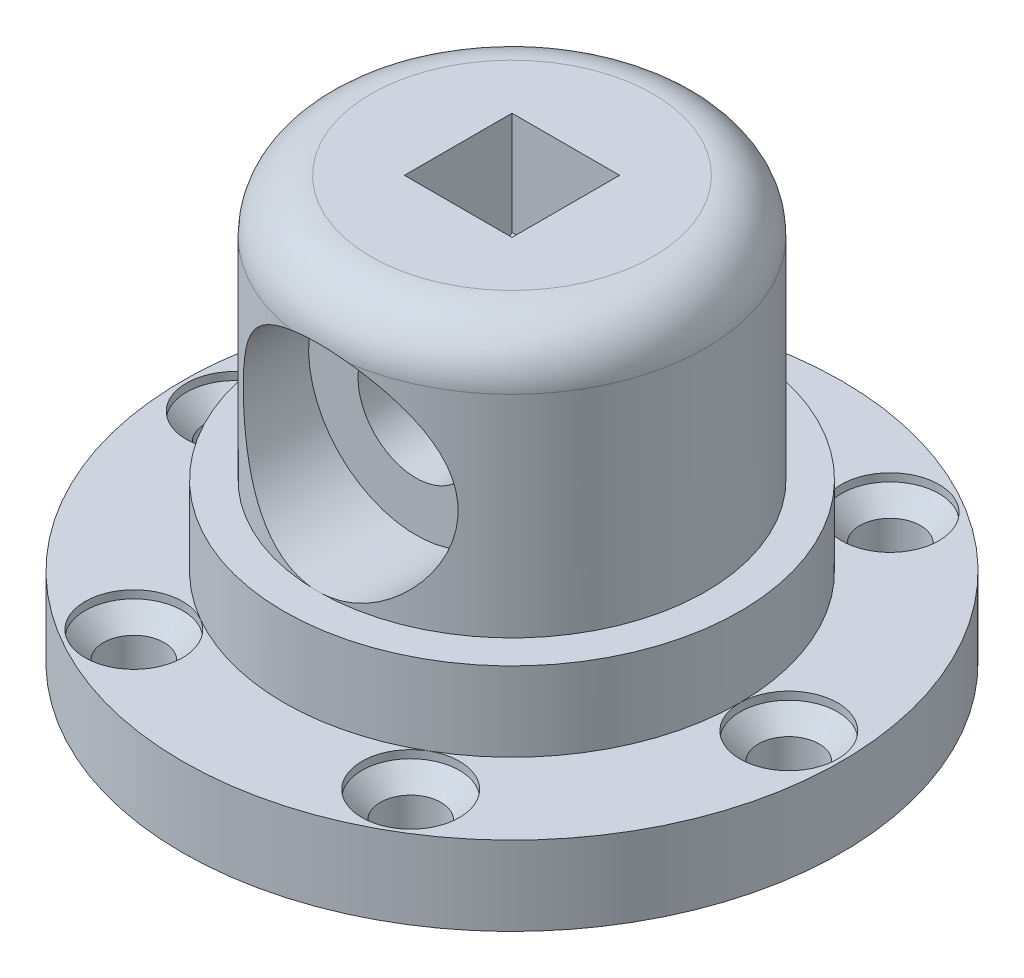
SolidWorks part; units mm, degrees
material "尼龙 101"
ref_plane "前视基准面" through (0, 0, 0) normal (0, 0, 1) x (1, 0, 0)
ref_plane "上视基准面" through (0, 0, 0) normal (0, 1, 0) x (1, 0, 0)
ref_plane "右视基准面" through (0, 0, 0) normal (1, 0, 0) x (0, 0, -1)
sketch "草图1" plane through (0, 0, 0) normal (0, 1, 0) x (1, 0, 0)
  circle A0 centre (0, 0) radius 12.5
  dimension "D1" = 25
extrude "凸台-拉伸1" add sketch "草图1" along normal blind 6
sketch "草图2" plane through (0, 6, 0) normal (0, 1, 0) x (1, 0, 0)
  line L0 (4.1, 4.1) -> (-4.1, 4.1) construction
  line L1 (2.5, 2.5) -> (-2.5, 2.5) construction
  line L2 (2.5, 2.5) -> (2.5, -2.5) construction
  line L3 (2.5, -2.5) -> (-2.5, -2.5) construction
  line L4 (-2.5, 2.5) -> (-2.5, -2.5) construction
  line L5 (2.5, 2.5) -> (-2.5, -2.5) construction
  line L6 (2.5, -2.5) -> (-2.5, 2.5) construction
  line L7 (-4.1, 4.1) -> (-4.1, -4.1) construction
  line L8 (4.1, -4.1) -> (-4.1, -4.1) construction
  line L9 (4.1, 4.1) -> (4.1, -4.1) construction
  line L11 (4.1, 4.1) -> (-4.1, 4.1) construction
  line L12 (4.1, 4.1) -> (4.1, 6.1) construction
  line L13 (4.1, 6.1) -> (-4.1, 6.1) construction
  line L14 (-4.1, 4.1) -> (-4.1, 6.1) construction
  circle A0 centre (0, 0) radius 5.7983 construction
  circle A1 centre (0, 0) radius 7.3498
  point P0 (0, 0)
  dimension "D1" = 5
  dimension "D2" = 5
  dimension "D4" = 2
  dimension "D3" = 1.6
sketch "草图3" plane through (0, 0, 0) normal (0, -1, 0) x (-1, 0, 0)
  circle A0 centre (0, 0) radius 7.5
  dimension "D1" = 15
sketch "草图4" plane through (0, 6, 0) normal (0, 1, 0) x (1, 0, 0)
  circle A0 centre (-10.5, 0) radius 1.15
  dimension "D1" = 2.3
  dimension "D2" = 10.5
extrude "切除-拉伸2" cut sketch "草图4" against normal blind 19 contours A0
extrude "切除-拉伸3" cut sketch "草图3" against normal blind 5 contours A0
chamfer "倒角2" distance 0.7 angle 45 1 edges at (-10.5, 6, 1.15)
sketch "草图8" plane through (0, 6, 0) normal (0, 1, 0) x (1, 0, 0)
  circle A0 centre (0, 0) radius 8.65
  circle A1 centre (0, 0) radius 17.4543
  dimension "D1" = 17.3
extrude "切除-拉伸4" cut sketch "草图8" against normal blind 3
pattern_circular "阵列(圆周)2" count 6 over 360 about axis through (0, 3, 0) along (0, 1, 0) of "切除-拉伸2"
extrude "凸台-拉伸2" add sketch "草图2" along normal blind 10 contours A1
sketch "草图9" plane through (0, 3, 0) normal (0, 1, 0) x (1, 0, 0)
  circle A0 centre (-10.5, 0) radius 1.85
extrude "切除-拉伸5" cut sketch "草图9" against normal blind 0.3
chamfer "倒角3" distance 0.7 angle 45 1 edges at (-10.5, 2.7, 1.15)
pattern_circular "阵列(圆周)3" count 6 over 360 about axis through (0, 6, 0) along (0, -1, 0) of "切除-拉伸5" reverse direction yes
chamfer "倒角4" distance 0.7 angle 45 5 edges at (5.25, 2.7, 10.2433) (10.5, 2.7, 1.15) (5.25, 2.7, -7.9433) (-5.25, 2.7, -7.9433) (-5.25, 2.7, 10.2433)
sketch "草图10" plane through (0, 16, 0) normal (0, 1, 0) x (1, 0, 0)
  line L1 (2.04, 2.04) -> (-2.04, 2.04)
  line L2 (2.04, 2.04) -> (2.04, -2.04)
  line L3 (2.04, -2.04) -> (-2.04, -2.04)
  line L4 (-2.04, 2.04) -> (-2.04, -2.04)
  line L5 (2.04, 2.04) -> (-2.04, -2.04) construction
  line L6 (2.04, -2.04) -> (-2.04, 2.04) construction
  point P0 (0, 0)
  dimension "D1" = 4.08
  dimension "D2" = 4.08
extrude "切除-拉伸6" cut sketch "草图10" against normal blind 8
sketch "草图11" plane through (0, 0, 0) normal (1, 0, 0) x (0, 0, -1)
  line L0 (-0.3049, 10.075) -> (-10.8741, 10.075)
  line L1 (-10.8741, 10.075) -> (-10.8741, 6)
  line L2 (-10.8741, 6) -> (-3.64, 6)
  line L3 (-3.64, 6) -> (-3.64, 7.875)
  line L4 (-3.64, 7.875) -> (-2.04, 7.875)
  line L5 (-2.04, 7.875) -> (-2.04, 9.125)
  line L6 (8.65, 6) -> (-8.65, 6) construction
  line L7 (-0.3049, 10.075) -> (11.1257, 10.075)
  line L8 (11.1257, 10.075) -> (11.1257, 9.125)
  line L9 (11.1257, 9.125) -> (-2.04, 9.125)
  dimension "D1" = 4.075
  dimension "D2" = 2.2
  dimension "D3" = 1.6
  dimension "D4" = 0
  dimension "D5" = 0.95
  dimension "D6" = 0
revolve "切除-旋转1" cut sketch "草图11" angle 360 about L0
fillet "圆角1" radius 2 1 edges at (0, 16, 7.3498)
chamfer "倒角5" distance 4.08 angle 45 1 edges at (0, 8, -2.04)
